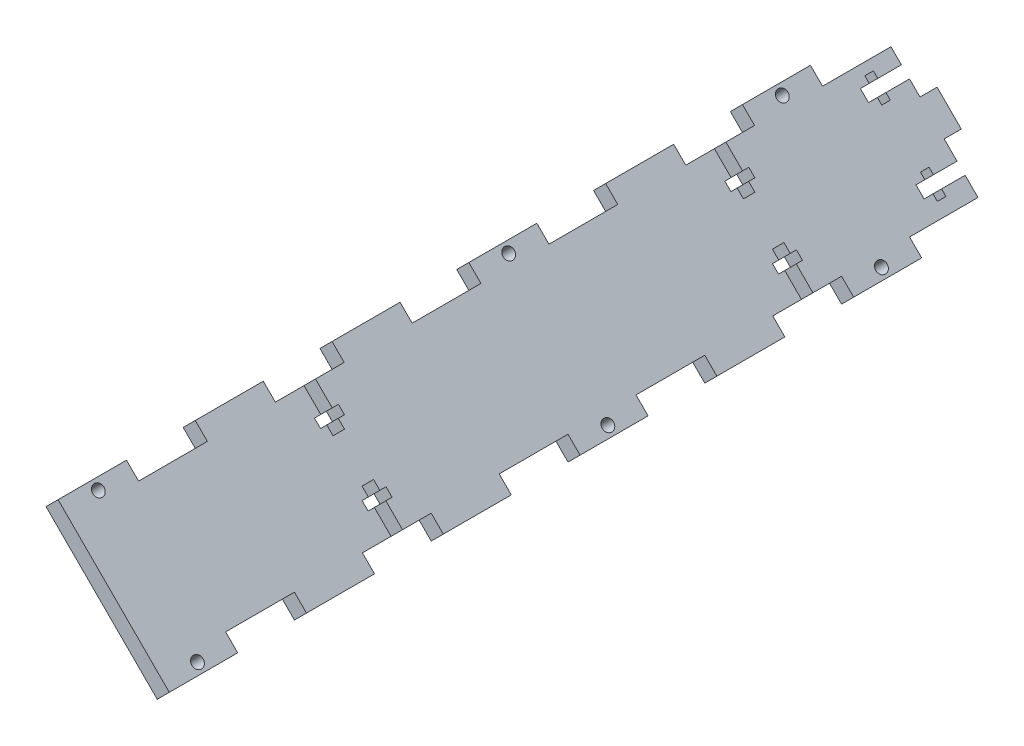
SolidWorks part; units mm, degrees
ref_plane "Front Plane" through (0, 0, 0) normal (0, 0, 1) x (1, 0, 0)
ref_plane "Top Plane" through (0, 0, 0) normal (0, 1, 0) x (1, 0, 0)
ref_plane "Right Plane" through (0, 0, 0) normal (1, 0, 0) x (0, 0, -1)
sketch "Sketch1" plane through (0, 0, 0) normal (0, 0, 1) x (1, 0, 0)
  line L0 (66.9029, 45.85) -> (108.2121, 4.5408)
  line L1 (66.9029, 45.85) -> (71.393, 50.3401)
  line L2 (108.2121, 4.5408) -> (112.7022, 9.0309)
  line L3 (71.393, 50.3401) -> (112.7022, 9.0309)
  line L4 (76.7812, -26.8901) -> (72.2911, -22.4) construction
extrude "Boss-Extrude1" add sketch "Sketch1" along normal up to surface (304.8 mm away)
sketch "Sketch2" plane through (60.8666, 60.8666, 0) normal (0.7071, 0.7071, 0) x (0, 0, -1)
  line L0 (-304.8, -14.8867) -> (0, -14.8867) construction
  line L1 (-279.4, -21.2367) -> (-253.8574, -21.2367)
  line L2 (-279.4, -21.2367) -> (-279.4, -14.8867)
  line L3 (-279.4, -14.8867) -> (-253.8574, -14.8867)
  line L4 (-253.8574, -21.2367) -> (-253.8574, -14.8867)
  line L5 (-304.8, -73.3067) -> (0, -73.3067) construction
  line L6 (-279.4, -66.9567) -> (-253.8574, -66.9567)
  line L7 (-279.4, -66.9567) -> (-279.4, -73.3067)
  line L8 (-279.4, -73.3067) -> (-253.8574, -73.3067)
  line L9 (-253.8574, -66.9567) -> (-253.8574, -73.3067)
extrude "Cut-Extrude1" cut sketch "Sketch2" against normal blind 6.35
pattern_linear "LPattern1" count 6 spacing 50.8 along (0, 0, -1) of "Cut-Extrude1"
sketch "Sketch3" plane through (0, 0, 0) normal (0, 0, -1) x (-1, 0, 0)
  line L0 (-82.1811, 30.5718) -> (-91.1613, 21.5915)
  line L1 (-71.393, 41.3598) -> (-103.722, 9.0309) construction
  line L2 (-91.1613, 21.5915) -> (-95.6515, 26.0817)
  line L3 (-108.2121, 13.521) -> (-75.8832, 45.85) construction
  line L4 (-95.6515, 26.0817) -> (-86.6712, 35.0619)
  line L5 (-86.6712, 35.0619) -> (-82.1811, 30.5718)
  dimension "D1" = 21.6066
  dimension "D2" = 12.7
extrude "Boss-Extrude2" add sketch "Sketch3" along normal blind 6.35
sketch "Sketch4" plane through (56.3764, 56.3764, 0) normal (-0.7071, -0.7071, 0) x (-0.7071, 0.7071, 0)
  line L0 (-28.865, -4.261) -> (-28.865, -30.7468) construction
  line L1 (-58.075, -4.261) -> (-58.075, -30.7468) construction
  line L2 (-66.9567, 0) -> (-66.9567, -25.4) construction
  line L3 (-49.1933, 6.35) -> (-49.1933, 0) construction
  line L4 (-36.4933, 6.35) -> (-36.4933, 0) construction
  line L5 (-21.2367, -25.4) -> (-21.2367, 0) construction
  line L6 (-49.1933, 0) -> (-66.9567, 0) construction
  line L7 (-21.2367, 0) -> (-36.4933, 0) construction
  line B0 (-55.9414, 0) -> (-60.2086, 0)
  line B1 (-60.2086, -11.938) -> (-62.52, -11.938)
  line B2 (-62.52, -11.938) -> (-62.52, -8.763)
  line B3 (-62.52, -8.763) -> (-60.2086, -8.763)
  line B4 (-60.2086, -8.763) -> (-60.2086, 0)
  line B5 (-60.2086, -11.938) -> (-60.2086, -15.24)
  line B6 (-60.2086, -15.24) -> (-55.9414, -15.24)
  line B7 (-55.9414, -11.938) -> (-55.9414, -15.24)
  line B8 (-55.9414, -8.763) -> (-55.9414, 0)
  line B9 (-53.63, -8.763) -> (-55.9414, -8.763)
  line B10 (-53.63, -11.938) -> (-53.63, -8.763)
  line B11 (-55.9414, -11.938) -> (-53.63, -11.938)
  line B12 (-26.7314, 0) -> (-30.9986, 0)
  line B13 (-30.9986, -11.938) -> (-33.31, -11.938)
  line B14 (-33.31, -11.938) -> (-33.31, -8.763)
  line B15 (-33.31, -8.763) -> (-30.9986, -8.763)
  line B16 (-30.9986, -8.763) -> (-30.9986, 0)
  line B17 (-30.9986, -11.938) -> (-30.9986, -15.24)
  line B18 (-30.9986, -15.24) -> (-26.7314, -15.24)
  line B19 (-26.7314, -11.938) -> (-26.7314, -15.24)
  line B20 (-26.7314, -8.763) -> (-26.7314, 0)
  line B21 (-24.42, -8.763) -> (-26.7314, -8.763)
  line B22 (-24.42, -11.938) -> (-24.42, -8.763)
  line B23 (-26.7314, -11.938) -> (-24.42, -11.938)
sketch_block_instance "TSlot-1"
sketch_block "TSlot" parameters "D1"=3.302, "D2"=3.175
sketch_block_instance "TSlot-2"
extrude "Cut-Extrude2" cut sketch "Sketch4" against normal through all
sketch "Sketch5" plane through (56.3764, 56.3764, 0) normal (-0.7071, -0.7071, 0) x (-0.7071, 0.7071, 0)
  line L0 (-14.8867, -289.9664) -> (-21.2367, -294.2336) construction
  line L1 (-14.8867, -304.8) -> (-14.8867, -279.4) construction
  line L2 (-21.2367, -289.9664) -> (-14.8867, -289.9664) construction
  line L3 (-21.2367, -289.9664) -> (-14.8867, -294.2336) construction
  line L4 (-21.2367, -294.2336) -> (-14.8867, -294.2336) construction
  line L5 (-21.2367, -137.5664) -> (-14.8867, -141.8336) construction
  line L6 (-14.8867, -152.2574) -> (-14.8867, -127) construction
  line L7 (-21.2367, -141.8336) -> (-14.8867, -141.8336) construction
  line L8 (-21.2367, -141.8336) -> (-14.8867, -137.5664) construction
  line L9 (-21.2367, -152.4) -> (-21.2367, -141.8336) construction
  line L10 (-21.2367, -137.5664) -> (-14.8867, -137.5664) construction
  line L11 (-21.2367, -40.2336) -> (-14.8867, -35.9664) construction
  line L12 (-14.8867, -50.6574) -> (-14.8867, -25.4) construction
  line L13 (-21.2367, -35.9664) -> (-14.8867, -35.9664) construction
  line L14 (-21.2367, -35.9664) -> (-14.8867, -40.2336) construction
  line L15 (-21.2367, -40.2336) -> (-14.8867, -40.2336) construction
  circle A0 centre (-18.0617, -38.1) radius 2.0955
  circle A1 centre (-18.0617, -139.7) radius 2.0955
  circle A2 centre (-18.0617, -292.1) radius 2.0955
  dimension "D1" = 4.191
extrude "Cut-Extrude3" cut sketch "Sketch5" against normal through all
ref_plane "Midplane" through (31.1811, -31.1811, 0) normal (0.7071, -0.7071, 0) x (0, 0, -1)
mirror "Mirror1" about plane through (31.1811, -31.1811, 0) normal (0.7071, -0.7071, 0) of "Cut-Extrude3"
sketch "Sketch6" plane through (56.3764, 56.3764, 0) normal (-0.7071, -0.7071, 0) x (-0.7071, 0.7071, 0)
  line L0 (0, -215.8287) -> (-47.8431, -215.8287) construction
  line L1 (32.2115, -63.4287) -> (-38.3785, -63.4287) construction
  line L2 (-21.2367, -50.6574) -> (-14.8867, -50.6574) construction
  line L3 (-14.8867, -76.2) -> (-21.2367, -76.2) construction
  line L4 (-21.2367, -203.0574) -> (-14.8867, -203.0574) construction
  line L5 (-14.8867, -228.6) -> (-21.2367, -228.6) construction
  line L6 (-21.2367, -76.2) -> (-21.2367, -50.6574) construction
  line L7 (-21.2367, -228.6) -> (-21.2367, -203.0574) construction
  line B0 (-21.2367, -65.5623) -> (-21.2367, -61.2951)
  line B1 (-33.1747, -61.2951) -> (-33.1747, -58.9837)
  line B2 (-33.1747, -58.9837) -> (-29.9997, -58.9837)
  line B3 (-29.9997, -58.9837) -> (-29.9997, -61.2951)
  line B4 (-29.9997, -61.2951) -> (-21.2367, -61.2951)
  line B5 (-33.1747, -61.2951) -> (-36.4767, -61.2951)
  line B6 (-36.4767, -61.2951) -> (-36.4767, -65.5623)
  line B7 (-33.1747, -65.5623) -> (-36.4767, -65.5623)
  line B8 (-29.9997, -65.5623) -> (-21.2367, -65.5623)
  line B9 (-29.9997, -67.8737) -> (-29.9997, -65.5623)
  line B10 (-33.1747, -67.8737) -> (-29.9997, -67.8737)
  line B11 (-33.1747, -65.5623) -> (-33.1747, -67.8737)
  line B12 (-21.2367, -217.9623) -> (-21.2367, -213.6951)
  line B13 (-33.1747, -213.6951) -> (-33.1747, -211.3837)
  line B14 (-33.1747, -211.3837) -> (-29.9997, -211.3837)
  line B15 (-29.9997, -211.3837) -> (-29.9997, -213.6951)
  line B16 (-29.9997, -213.6951) -> (-21.2367, -213.6951)
  line B17 (-33.1747, -213.6951) -> (-36.4767, -213.6951)
  line B18 (-36.4767, -213.6951) -> (-36.4767, -217.9623)
  line B19 (-33.1747, -217.9623) -> (-36.4767, -217.9623)
  line B20 (-29.9997, -217.9623) -> (-21.2367, -217.9623)
  line B21 (-29.9997, -220.2737) -> (-29.9997, -217.9623)
  line B22 (-33.1747, -220.2737) -> (-29.9997, -220.2737)
  line B23 (-33.1747, -217.9623) -> (-33.1747, -220.2737)
sketch_block_instance "TSlot-3"
sketch_block_instance "TSlot-4"
extrude "Cut-Extrude4" cut sketch "Sketch6" against normal through all
mirror "Mirror2" about plane through (31.1811, -31.1811, 0) normal (0.7071, -0.7071, 0) of "Cut-Extrude4"
